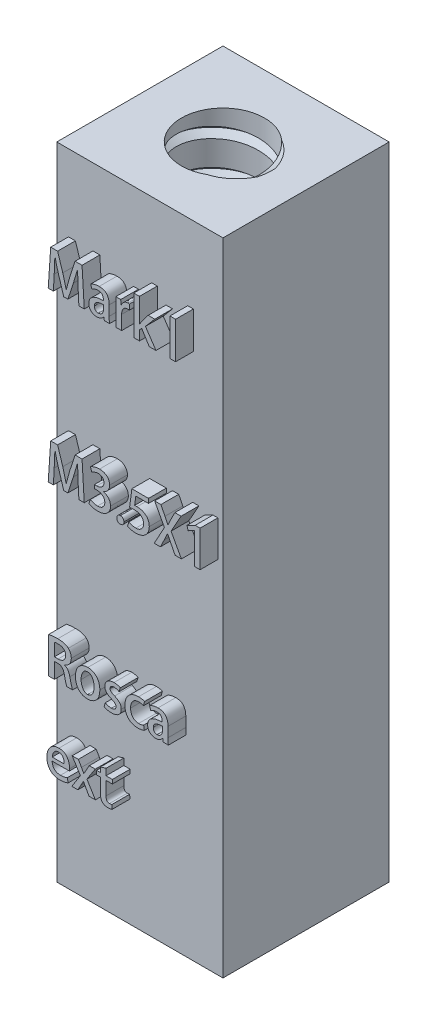
SolidWorks part; units mm, degrees
ref_plane "Alzado" through (0, 0, 0) normal (0, 0, 1) x (1, 0, 0)
ref_plane "Planta" through (0, 0, 0) normal (0, 1, 0) x (1, 0, 0)
ref_plane "Vista lateral" through (0, 0, 0) normal (1, 0, 0) x (0, 0, -1)
sketch "Croquis1" plane through (0, 0, 0) normal (0, 1, 0) x (1, 0, 0)
  line L1 (-3.5, 3.5) -> (3.5, 3.5)
  line L2 (-3.5, 3.5) -> (-3.5, -3.5)
  line L3 (-3.5, -3.5) -> (3.5, -3.5)
  line L4 (3.5, 3.5) -> (3.5, -3.5)
  line L5 (-3.5, 3.5) -> (3.5, -3.5) construction
  line L6 (-3.5, -3.5) -> (3.5, 3.5) construction
  circle A0 centre (0, 0) radius 1.75
  point P0 (0, 0)
  dimension "D1" = 3.5
  dimension "7" = 7
extrude "Saliente-Extruir1" add sketch "Croquis1" along normal blind 27
sketch "Croquis2" plane through (0, 0, 3.5) normal (0, 0, 1) x (1, 0, 0)
  text T0 "Mark I\r\n \r\nM3.5X1\r\n\r\nRosca\r\next" font "@Adobe Heiti Std R" height in points 5
split line "Línea de partición1"
extrude "Saliente-Extruir2" add sketch "Croquis2<2>" along normal blind 0.75
sketch "Croquis2<2>" plane through (0, 0, 3.5) normal (0, 0, 1) x (1, 0, 0) same geometry as "Croquis2"
thread "Rosca1" pitch 0.6 method cut profile "Perfil de rosca1" start angle 0, offset 1, length 18, pitch 1.5, diameter 3.5
ref_plane "Plano1" through (-1.75, 28, 0) normal (0, 0, 1) x (-1, 0, 0)
sketch "Perfil de rosca1" plane through (-1.75, 28, 0) normal (0, 0, 1) x (-1, 0, 0)
  line L0 (0, 0) -> (0, 0.6) construction
  line L1 (0, 0) -> (0.3248, 0.1875)
  line L2 (0.3248, 0.1875) -> (0.3248, 0.2625)
  line L3 (0.3248, 0.2625) -> (0, 0.45)
  line L4 (0.3248, 0.225) -> (0, 0.225) construction
  line L11 (0, 0) -> (0, 0.45)
  point P2 (0, 0)
  dimension "Pitch" = 0.6
  dimension "Profile_Angle" = 60
  dimension "Profile_Land" = 0.075
  dimension "Profile_Height" = 0.3248
